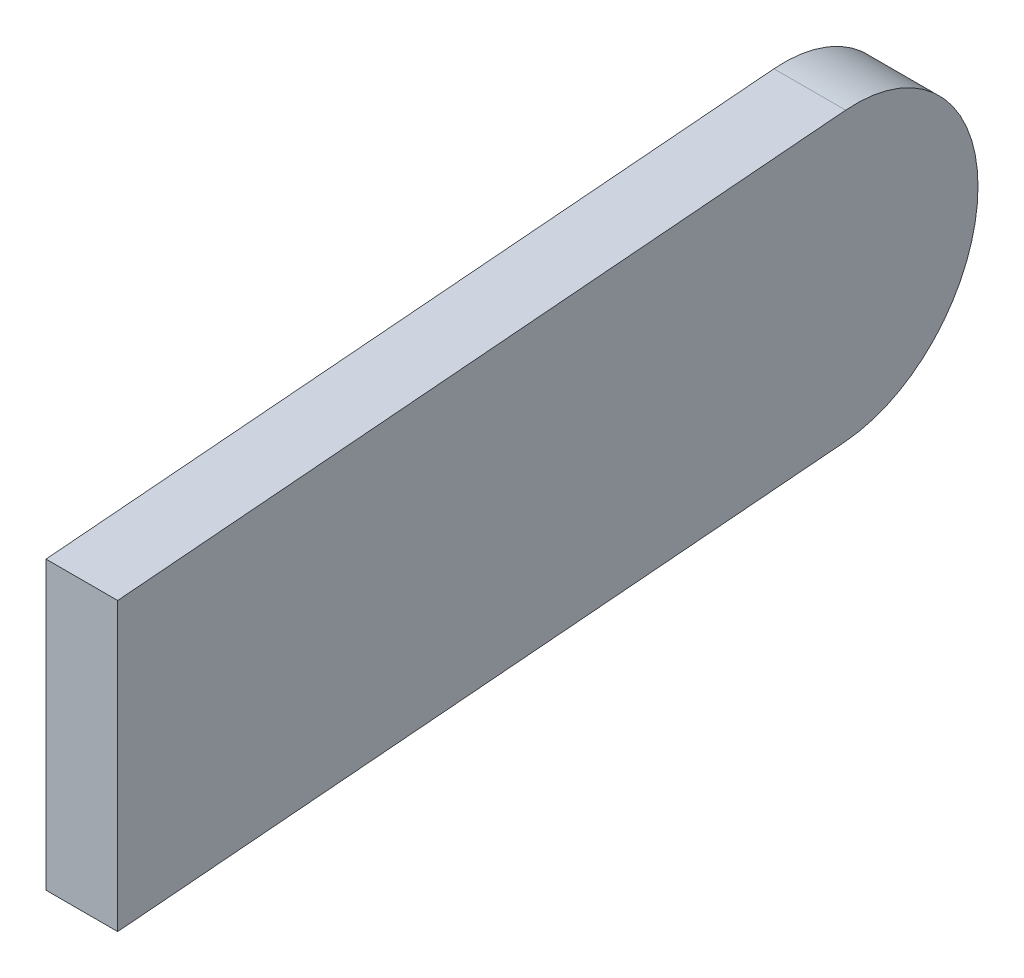
SolidWorks part; units mm, degrees
ref_plane "Front Plane" through (0, 0, 0) normal (0, 0, 1) x (1, 0, 0)
ref_plane "Top Plane" through (0, 0, 0) normal (0, 1, 0) x (1, 0, 0)
ref_plane "Right Plane" through (0, 0, 0) normal (1, 0, 0) x (0, 0, -1)
sketch "Sketch1" plane through (0, 0, 0) normal (0, 1, 0) x (1, 0, 0)
  line L0 (-0.2, 1.3) -> (0, 1.3)
  line L1 (0, -1.3) -> (0.2, -1.3)
  line L2 (-0.2, 1.3) -> (0, -1.3)
  line L3 (0, 1.3) -> (0.2, -1.3)
  dimension "D1" = 1.3
  dimension "D2" = 1.3
  dimension "D3" = 0.2
extrude "Boss-Extrude1" add sketch "Sketch1" along normal mid plane 0.8
fillet "Fillet1" radius 0.4 2 edges at (-0.1, 0.4, -1.3) (-0.1, -0.4, -1.3)
